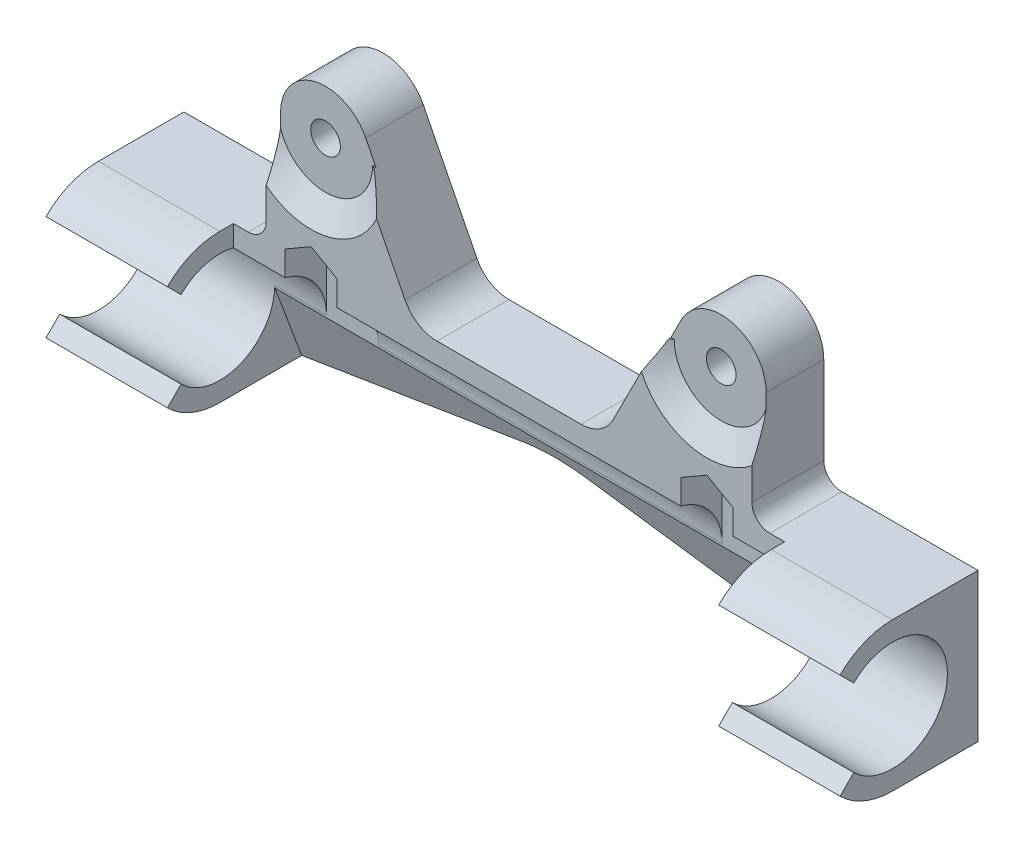
SolidWorks part; units mm, degrees
ref_plane "Front Plane" through (0, 0, 0) normal (0, 0, 1) x (1, 0, 0)
ref_plane "Top Plane" through (0, 0, 0) normal (0, 1, 0) x (1, 0, 0)
ref_plane "Right Plane" through (0, 0, 0) normal (1, 0, 0) x (0, 0, -1)
sketch "Sketch1" plane through (0, 0, 0) normal (-1, 0, 0) x (0, 0, 1)
  line L0 (-9.5, 8.25) -> (-9.5, -8.25)
  line L1 (0, 8.25) -> (-9.5, 8.25)
  line L2 (0, -8.25) -> (-9.5, -8.25)
  arc A4 (0, -8.25) -> (0, 8.25) centre (0, 0) ccw
  dimension "D2" = 16.5
  dimension "D3" = 9.5
extrude "Boss-Extrude1" add sketch "Sketch1" along normal blind 88.3
hole_wizard "Ø2.7 (2.7) Diameter Hole1" [suppressed] positions "Sketch5" profile "Sketch4" hole size "Ø2.7" standard "Ansi Metric"
sketch "Sketch5" [suppressed] plane through (-9.5, 0, 0) normal (-1, 0, 0) x (0, 0, 1)
  line L1 (2.5, -5) -> (11, -5) construction
  line L2 (2.5, -5) -> (2.5, 5) construction
  line L3 (2.5, 5) -> (11, 5) construction
  line L4 (11, -5) -> (11, 5) construction
  line L5 (0, 0) -> (2.5, 0) construction
  line L7 (-8.25, 0) -> (8.25, 0) construction
  line L10 (13.5, 0) -> (11, 0) construction
  line L11 (-8.25, 13.5) -> (8.25, 13.5) construction
  point P0 (2.5, -5)
  point P89 (2.5, 5)
  point P91 (11, 5)
  point P93 (11, -5)
  dimension "D1" = 2.5
  dimension "D2" = 10
sketch "Sketch4" plane through (-9.5, -5, 2.5) normal (0, 1, 0) x (0, 0, 1)
  line L0 (0, 0) -> (0, 4.8112)
  line L1 (0, 4.8112) -> (1.35, 4)
  line L2 (1.35, 4) -> (1.35, 0)
  line L5 (1.35, 0) -> (0, 0)
  line L10 (0, 4.8112) -> (-1.35, 4) construction
  line L11 (0, -6.35) -> (0, 107.95) construction
  dimension "Hole Dia." = 2.7
  dimension "Hole Depth" = 4
  dimension "Drill Angle" = 118
sketch "Sketch6" plane through (0, 0, -9.5) normal (0, 0, -1) x (-1, 0, 0)
  line L0 (44.15, -8.25) -> (44.15, 27.1722) construction
  line L1 (88.3, -8.25) -> (0, -8.25) construction
  line L3 (17.15, -8.25) -> (17.15, 20)
  line L4 (26.6127, 22.2549) -> (32.5796, 10.4461)
  line L5 (17.15, -8.25) -> (71.15, -8.25)
  line L7 (36.1497, 8.25) -> (52.1503, 8.25)
  line L8 (88.3, 8.25) -> (0, 8.25) construction
  line L10 (61.6873, 22.2549) -> (55.7204, 10.4461)
  line L11 (71.15, -8.25) -> (71.15, 20)
  circle A0 centre (22.15, 20) radius 1.65
  arc A2 (26.6127, 22.2549) -> (17.15, 20) centre (22.15, 20) ccw
  arc A3 (32.5796, 10.4461) -> (36.1497, 8.25) centre (36.1497, 12.25) ccw
  arc A4 (55.7204, 10.4461) -> (52.1503, 8.25) centre (52.1503, 12.25) cw
  arc A5 (61.6873, 22.2549) -> (71.15, 20) centre (66.15, 20) cw
  circle A7 centre (66.15, 20) radius 1.65
  point P28 (44.15, 8.25)
  dimension "D4" = 20
  dimension "D5" = 5
  dimension "D6" = 4
extrude "Boss-Extrude2" add sketch "Sketch6" against normal blind 8
sketch "Sketch7" plane through (-88.3, 0, 0) normal (-1, 0, 0) x (0, 0, 1)
  line L0 (13.4819, 13.4819) -> (4.3134, 4.3134)
  line L1 (4.3134, -4.3134) -> (13.4819, -13.4819)
  line L2 (13.4819, -13.4819) -> (13.4819, 13.4819)
  line L3 (0, 0) -> (4.3134, 4.3134) construction
  line L4 (0, 0) -> (4.3134, -4.3134) construction
  arc A0 (4.3134, 4.3134) -> (4.3134, -4.3134) centre (0, 0) ccw
  dimension "D1" = 6.1
extrude "Cut-Extrude1" cut sketch "Sketch7" against normal through all
sketch "Sketch8" plane through (0, 0, -1.5) normal (0, 0, 1) x (1, 0, 0)
  line L0 (-88.3, 8.25) -> (0, 8.25) construction
  line L1 (-74.8, -13.234) -> (-13.5, -13.234)
  line L2 (-74.8, -13.234) -> (-74.8, 8.25)
  line L3 (-74.8, 8.25) -> (-13.5, 8.25)
  line L4 (-13.5, -13.234) -> (-13.5, 8.25)
  line L5 (-88.3, 6.1) -> (-88.3, -6.1) construction
  dimension "D1" = 13.5
  dimension "D2" = 13.5
extrude "Cut-Extrude2" cut sketch "Sketch8" along normal through all
ref_plane "Plane1" through (0, 0, -6.1) normal (0, 0, -1) x (-1, 0, 0)
sketch "Sketch9" plane through (0, 0, -6.1) normal (0, 0, -1) x (-1, 0, 0)
  line L1 (13.5, 0) -> (74.8, 0)
  line L2 (13.5, 0) -> (13.5, -11.6994)
  line L3 (13.5, -11.6994) -> (74.8, -11.6994)
  line L4 (74.8, 0) -> (74.8, -11.6994)
extrude "Cut-Extrude3" cut sketch "Sketch9" against normal through all
sketch "Sketch10" plane through (0, 0, -9.5) normal (0, 0, -1) x (-1, 0, 0)
  line L0 (22.15, 7) -> (66.15, 7) construction
  line L1 (44.15, 7) -> (44.15, -8.25) construction
  line L2 (88.3, -8.25) -> (0, -8.25) construction
  circle A0 centre (22.15, 7) radius 1.65
  circle A1 centre (66.15, 7) radius 1.65
  circle A2 centre (22.15, 20) radius 1.65 construction
  dimension "D2" = 3.3
  dimension "D1" = 44
  dimension "D3" = 13
extrude "Cut-Extrude4" cut sketch "Sketch10" against normal through all
chamfer "Chamfer1" distance 8 distance2 3 1 edges at (-44.15, -8.25, -6.1) first distance on face at (-44.15, -4.125, -6.1)
sketch "Sketch11" plane through (0, 0, -6.1) normal (0, 0, -1) x (-1, 0, 0)
  line L0 (74.8, -8.25) -> (47.5959, -1.8288)
  line L2 (40.7041, -1.8288) -> (13.5, -8.25)
  line L3 (13.5, -8.25) -> (13.5, -16.4277)
  line L4 (13.5, -16.4277) -> (74.8, -16.4277)
  line L5 (74.8, -16.4277) -> (74.8, -8.25)
  arc A0 (40.7041, -1.8288) -> (47.5959, -1.8288) centre (44.15, -16.4277) cw
  dimension "D1" = 15
extrude "Cut-Extrude5" cut sketch "Sketch11" along normal through all
fillet "Fillet1" radius 2 2 edges at (-71.15, 8.25, -5.5) (-17.15, 8.25, -5.5)
sketch "Sketch12" plane through (0, 0, -9.5) normal (0, 0, -1) x (-1, 0, 0)
  line L1 (22.15, 16.6514) -> (25.05, 18.3257)
  line L2 (25.05, 18.3257) -> (25.05, 21.6743)
  line L3 (25.05, 21.6743) -> (22.15, 23.3486)
  line L4 (22.15, 23.3486) -> (19.25, 21.6743)
  line L5 (19.25, 21.6743) -> (19.25, 18.3257)
  line L6 (19.25, 18.3257) -> (22.15, 16.6514)
  line L7 (66.15, 16.6514) -> (69.05, 18.3257)
  line L8 (69.05, 18.3257) -> (69.05, 21.6743)
  line L9 (69.05, 21.6743) -> (66.15, 23.3486)
  line L10 (66.15, 23.3486) -> (63.25, 21.6743)
  line L11 (63.25, 21.6743) -> (63.25, 18.3257)
  line L12 (63.25, 18.3257) -> (66.15, 16.6514)
  circle A0 centre (22.15, 20) radius 2.9 construction
  circle A1 centre (66.15, 20) radius 2.9 construction
  circle A2 centre (22.15, 20) radius 1.65 construction
  circle A3 centre (66.15, 20) radius 1.65 construction
  dimension "D1" = 5.8
extrude "Cut-Extrude6" cut sketch "Sketch12" against normal blind 3
sketch "Sketch13" plane through (0, 0, -1.5) normal (0, 0, 1) x (1, 0, 0)
  line L1 (-69.05, -2.124) -> (-63.25, -2.124)
  line L4 (-25.05, -2.124) -> (-19.25, -2.124)
  line L7 (-66.15, 10.3486) -> (-69.05, 8.6743)
  line L8 (-69.05, 8.6743) -> (-69.05, -2.124)
  line L11 (-63.25, -2.124) -> (-63.25, 8.6743)
  line L12 (-63.25, 8.6743) -> (-66.15, 10.3486)
  line L13 (-22.15, 10.3486) -> (-25.05, 8.6743)
  line L14 (-25.05, 8.6743) -> (-25.05, -2.124)
  line L17 (-19.25, -2.124) -> (-19.25, 8.6743)
  line L18 (-19.25, 8.6743) -> (-22.15, 10.3486)
  line L19 (-69.05, 5.3257) -> (-66.15, 3.6514)
  line L20 (-66.15, 3.6514) -> (-63.25, 5.3257)
  line L21 (-25.05, 5.3257) -> (-22.15, 3.6514)
  line L22 (-22.15, 3.6514) -> (-19.25, 5.3257)
  arc A2 (-64.9089, 5.9127) -> (-67.3911, 5.9127) centre (-66.15, 7) ccw construction
  arc A3 (-20.9089, 5.9127) -> (-23.3911, 5.9127) centre (-22.15, 7) ccw construction
  circle A4 centre (-66.15, 7) radius 2.9 construction
  circle A5 centre (-22.15, 7) radius 2.9 construction
  dimension "D2" = 5.8
extrude "Cut-Extrude7" cut sketch "Sketch13" against normal up to surface (4.6 mm away) up to plane "Plane1"
sketch "Sketch14" plane through (0, 0, -1.5) normal (0, 0, 1) x (1, 0, 0)
  line L0 (-61.15, 20) -> (-27.15, 20)
  line L1 (-22.15, 25) -> (-66.15, 25)
  arc A0 (-66.15, 25) -> (-61.15, 20) centre (-66.15, 20) ccw
  arc A1 (-27.15, 20) -> (-22.15, 25) centre (-22.15, 20) ccw
  arc A2 (-61.6873, 22.2549) -> (-71.15, 20) centre (-66.15, 20) ccw construction
  arc A3 (-17.15, 20) -> (-26.6127, 22.2549) centre (-22.15, 20) ccw construction
extrude "Cut-Extrude8" cut sketch "Sketch14" against normal offset from surface (1.6 mm away) 6.4 up to face at (-66.15, 20, -9.5)
chamfer "Chamfer2" distance 3 angle 30 2 edges at (-22.15, 15, -1.5) (-66.15, 15, -1.5) first distance on face at (-44.15, 10.3544, -1.5)
